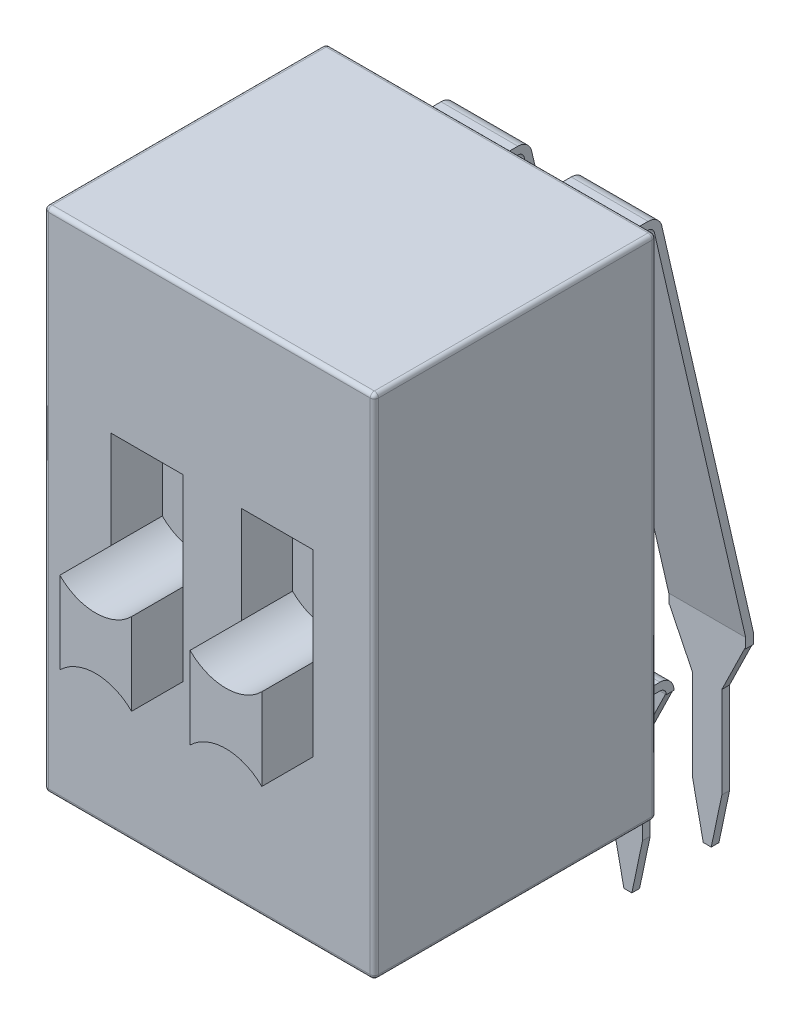
SolidWorks part; units mm, degrees
note: The reader was unsure of these and kept them because the rebuilt part matched: shared geometry of "Эскиз4<4>", "Эскиз5<4>".
ref_plane "Спереди" through (0, 0, 0) normal (0, 0, 1) x (1, 0, 0)
ref_plane "Сверху" through (0, 0, 0) normal (0, 1, 0) x (1, 0, 0)
ref_plane "Справа" through (0, 0, 0) normal (1, 0, 0) x (0, 0, -1)
sketch "Эскиз1" plane through (0, 0, 0) normal (1, 0, 0) x (0, 0, -1)
  line L0 (0, 0) -> (-2.75, 0) construction
  line L1 (-2.75, 4.95) -> (2.75, 4.95)
  line L2 (-2.75, 4.95) -> (-2.75, -4.95)
  line L3 (-2.75, -4.95) -> (2.75, -4.95)
  line L4 (2.75, 4.95) -> (2.75, -4.95)
  line L5 (0, 0) -> (0, -4.95) construction
  dimension "D1" = 5.5
  dimension "D2" = 9.9
extrude "Вытянуть1" add sketch "Эскиз1" along normal blind 6.44
sketch "Эскиз2" plane through (0, 0, -2.75) normal (0, 0, -1) x (-1, 0, 0)
  line L0 (-4.49, 4.95) -> (-4.49, -4.95) construction
  line L1 (-6.44, 4.95) -> (0, 4.95) construction
  line L2 (-6.44, -4.95) -> (0, -4.95) construction
  line L3 (-1.95, 4.95) -> (-1.95, -4.95) construction
  line L4 (-6.44, 3.95) -> (0, 3.95) construction
  line L5 (-6.44, -4.95) -> (-6.44, 4.95) construction
  line L6 (0, -4.95) -> (0, 4.95) construction
  line L7 (-6.44, -3.95) -> (0, -3.95) construction
  line L9 (-5.24, 4.025) -> (-3.74, 4.025)
  line L10 (-5.24, 4.025) -> (-5.24, 3.875)
  line L11 (-5.24, 3.875) -> (-3.74, 3.875)
  line L12 (-3.74, 4.025) -> (-3.74, 3.875)
  line L13 (-5.24, -3.875) -> (-3.74, -3.875) construction
  line L14 (-5.24, -3.875) -> (-5.24, -4.025) construction
  line L15 (-5.24, -4.025) -> (-3.74, -4.025) construction
  line L16 (-3.74, -3.875) -> (-3.74, -4.025) construction
  point P20 (-4.49, 3.875)
  point P21 (-3.74, 3.95)
  point P26 (-3.74, -3.95)
  point P27 (-4.49, -4.025)
  dimension "D1" = 1.95
  dimension "D2" = 1.95
  dimension "D3" = 2.54
  dimension "D4" = 1
  dimension "D5" = 1
  dimension "D6" = 1.5
  dimension "D7" = 0.15
sketch3d "Трехмерный эскиз1"
  line L1 (4.49, 3.95, -2.75) -> (4.49, 3.95, -3.7908)
  line L2 (4.49, 3.7949, -3.9857) -> (4.49, -3.95, -5.7697)
  line L3 (4.49, -3.95, -5.7697) -> (4.49, -7.85, -5.7697)
  line L4 (4.49, 4.95, -2.75) -> (4.49, -4.95, -2.75) construction
  line L5 (6.44, 3.95, -2.75) -> (0, 3.95, -2.75) construction
  line L6 (4.49, -3.95, -2.75) -> (4.49, -3.95, -12.5553) construction
  line L7 (4.49, -7.85, -3.0297) -> (4.49, -7.85, -12.4699) construction
  line L8 (6.44, -3.95, -2.75) -> (0, -3.95, -2.75) construction
  line L10 (6.44, 4.95, 2.75) -> (6.44, -4.95, 2.75) construction
  arc A1 (4.49, 3.95, -3.7908) -> (4.49, 3.7949, -3.9857) centre (4.49, 3.75, -3.7908) ccw
  point P22 (4.49, 3.95, -3.95)
  point P23 (4.29, 3.75, -3.7908)
  dimension "D1" = 8.74
  dimension "D2" = 2.9
sweep "По траектории1" add profiles "Эскиз2" path "Трехмерный эскиз1"
pattern_linear "Линейный массив1" count 2 spacing 2.54 along (-1, 0, 0) of "По траектории1"
sketch3d "Трехмерный эскиз2"
  line L0 (4.49, 4.95, -2.75) -> (4.49, -4.95, -2.75) construction
  line L1 (4.49, -3.95, -2.75) -> (4.49, -3.95, -4.0214)
  line L3 (6.44, -3.95, -2.75) -> (0, -3.95, -2.75) construction
  line L6 (4.49, -4.15, -4.2214) -> (4.49, -7.85, -4.2214)
  arc A0 (4.49, -3.95, -4.0214) -> (4.49, -4.15, -4.2214) centre (4.49, -4.15, -4.0214) ccw
  point P9 (4.49, -3.95, -4.2214)
  point P10 (4.29, -4.15, -4.0214)
  dimension "D1" = 0.2
sketch "Эскиз3" plane through (0, 0, -2.75) normal (0, 0, -1) x (-1, 0, 0)
  line L1 (-5.24, -3.875) -> (-3.74, -3.875)
  line L2 (-5.24, -3.875) -> (-5.24, -4.025)
  line L3 (-5.24, -4.025) -> (-3.74, -4.025)
  line L4 (-3.74, -3.875) -> (-3.74, -4.025)
sweep "По траектории2" add profiles "Эскиз3" path "Трехмерный эскиз2"
pattern_linear "Линейный массив2" count 2 spacing 2.54 along (-1, 0, 0) of "По траектории2"
sketch "Эскиз4" plane through (0, 0, -5.8447) normal (0, 0, -1) x (-1, 0, 0)
  line L0 (-4.49, -3.9415) -> (-4.49, -7.85) construction
  line L1 (-5.24, -3.9415) -> (-3.74, -3.9415) construction
  line L2 (-3.74, -7.85) -> (-5.24, -7.85) construction
  line L3 (-1.95, -3.9415) -> (-1.95, -7.85) construction
  line L4 (-2.7, -3.9415) -> (-1.2, -3.9415) construction
  line L5 (-1.2, -7.85) -> (-2.7, -7.85) construction
  line L6 (-1.8593, -7.85) -> (-2.0407, -7.85)
  line L7 (-2.25, -6.85) -> (-2.25, -5.0707)
  line L8 (-2.25, -5.0707) -> (-2.7, -4.15)
  line L9 (-2.0407, -7.85) -> (-2.25, -6.85)
  line L10 (-2.7, -4.15) -> (-1.2, -4.15) construction
  line L11 (-2.7, -3.9415) -> (-2.7, -7.85) construction
  line L12 (-5.24, -3.9415) -> (-5.24, -7.85) construction
  line L13 (-1.8593, -7.85) -> (-1.65, -6.85)
  line L14 (-1.65, -6.85) -> (-1.65, -5.0707)
  line L15 (-1.65, -5.0707) -> (-1.2, -4.15)
  line L16 (-1.2, -4.15) -> (-2.7, -4.15) construction
  line L17 (-5.24, -4.15) -> (-4.79, -5.0707)
  line L18 (-4.79, -5.0707) -> (-4.79, -6.85)
  line L19 (-4.79, -6.85) -> (-4.58, -7.85)
  line L20 (-4.58, -7.85) -> (-4.4, -7.85)
  line L21 (-4.19, -6.85) -> (-4.4, -7.85)
  line L22 (-4.19, -5.0707) -> (-4.19, -6.85)
  line L23 (-3.74, -4.15) -> (-4.19, -5.0707)
  line L24 (-5.24, -4.15) -> (-3.74, -4.15) construction
  point P17 (-1.95, -4.15)
  point P18 (-4.49, -4.15)
  dimension "D2" = 0.6
  dimension "D3" = 0.3
  dimension "D4" = 0.1814
  dimension "D5" = 0.09
extrude "Вырез-Вытянуть-Тонкостенный1" cut sketch "Эскиз4" along normal blind 0.15 and the other way blind 0.15 flip side to cut thin contours L15 L14 L13 L6 L9 L7 L8 thin type two direction wall 0.015 second wall 0.015
extrude "Вырез-Вытянуть-Тонкостенный4" cut sketch "Эскиз4<4>" against normal blind 0.15 and the other way blind 0.15 thin contours L17 L18 L19 L20 L21 L22 L23 thin type two direction wall 0.015 second wall 0.015
sketch "Эскиз4<4>" plane through (0, 0, -5.8447) normal (0, 0, -1) x (-1, 0, 0) same geometry as "Эскиз4"
sketch "Эскиз5" plane through (0, 0, -4.1464) normal (0, 0, 1) x (1, 0, 0)
  line L0 (1.2, -4.15) -> (1.65, -5.0707)
  line L1 (1.65, -5.0707) -> (1.65, -6.85)
  line L2 (1.65, -6.85) -> (1.8593, -7.85)
  line L3 (1.8593, -7.85) -> (2.0407, -7.85)
  line L4 (2.0407, -7.85) -> (2.25, -6.85)
  line L5 (2.25, -6.85) -> (2.25, -5.0707)
  line L6 (2.25, -5.0707) -> (2.7, -4.15)
  line L7 (2.7, -4.15) -> (1.2, -4.15) construction
  line L8 (3.74, -4.15) -> (5.24, -4.15) construction
  line L9 (5.24, -4.15) -> (4.79, -5.0707)
  line L10 (4.79, -5.0707) -> (4.79, -6.85)
  line L11 (4.79, -6.85) -> (4.58, -7.85)
  line L12 (4.58, -7.85) -> (4.4, -7.85)
  line L13 (4.4, -7.85) -> (4.19, -6.85)
  line L14 (4.19, -6.85) -> (4.19, -5.0707)
  line L15 (4.19, -5.0707) -> (3.74, -4.15)
  line L16 (4.49, -3.9415) -> (4.49, -7.85) construction
  line L17 (4.79, -5.0707) -> (4.19, -5.0707) construction
  line L18 (4.79, -6.85) -> (4.19, -6.85) construction
  line L19 (2.25, -5.0707) -> (1.65, -5.0707) construction
  line L20 (2.25, -6.85) -> (1.65, -6.85) construction
  line L21 (1.95, -3.9415) -> (1.95, -7.85) construction
  point P36 (1.95, -5.0707)
  point P37 (4.49, -5.0707)
  point P38 (4.49, -6.85)
  point P39 (1.95, -6.85)
  point P40 (4.49, -4.15)
  point P41 (1.95, -4.15)
  dimension "D1" = 0.6
  dimension "D2" = 0.6
  dimension "D3" = 0.18
  dimension "D4" = 0.1814
extrude "Вырез-Вытянуть-Тонкостенный5" cut sketch "Эскиз5" against normal blind 0.15 and the other way blind 0.15 thin contours L0 L1 L2 L3 L4 L5 L6
extrude "Вырез-Вытянуть-Тонкостенный6" cut sketch "Эскиз5<4>" against normal blind 0.15 and the other way blind 0.15 thin contours L9 L10 L11 L12 L13 L14 L15 thin type two direction wall 0.015 second wall 0.015
sketch "Эскиз5<4>" plane through (0, 0, -4.1464) normal (0, 0, 1) x (1, 0, 0) same geometry as "Эскиз5"
sketch "Эскиз6" plane through (0, 0, 2.75) normal (0, 0, 1) x (1, 0, 0)
  line L0 (1.95, -7.835) -> (1.95, 4.95) construction
  line L1 (2.0285, -7.835) -> (1.8715, -7.835) construction
  line L2 (6.44, 4.95) -> (0, 4.95) construction
  line L3 (4.49, -7.835) -> (4.49, 4.95) construction
  line L4 (4.4122, -7.835) -> (4.5678, -7.835) construction
  line L5 (0, 0) -> (6.44, 0) construction
  line L6 (1.3046, 1.75) -> (2.7046, 1.75)
  line L7 (1.3046, 1.75) -> (1.3046, -1.75)
  line L8 (1.3046, -1.75) -> (2.7046, -1.75)
  line L9 (2.7046, 1.75) -> (2.7046, -1.75)
  line L10 (6.44, 4.95) -> (6.44, -4.95) construction
  point P14 (1.3046, 0)
  dimension "D1" = 1.4
  dimension "D2" = 3.5
extrude "Вырез-Вытянуть1" cut sketch "Эскиз6" against normal blind 1
pattern_linear "Линейный массив3" count 2 spacing 2.54 along (1, 0, 0) of "Вырез-Вытянуть1"
sketch "Эскиз7" plane through (0, 0, 1.75) normal (0, 0, 1) x (1, 0, 0)
  line L2 (1.3046, -0.15) -> (1.3046, -1.75)
  line L4 (2.7046, -0.15) -> (2.7046, -1.75)
  line L9 (3.8446, -0.15) -> (3.8446, -1.75)
  line L11 (5.2446, -0.15) -> (5.2446, -1.75)
  arc A0 (1.3046, -1.75) -> (2.7046, -1.75) centre (2.0046, -2.45) cw
  arc A1 (1.3046, -0.15) -> (2.7046, -0.15) centre (2.0046, 0.55) ccw
  arc A2 (3.8446, -0.15) -> (5.2446, -0.15) centre (4.5446, 0.55) ccw
  arc A3 (3.8446, -1.75) -> (5.2446, -1.75) centre (4.5446, -2.45) cw
  dimension "D1" = 1.6
extrude "Вытянуть2" add sketch "Эскиз7" along normal blind 2
sketch "Эскиз8" plane through (0, 0, -2.75) normal (0, 0, -1) x (-1, 0, 0)
  line L0 (0, 0) -> (-6.4476, 0) construction
  line L1 (-5.9679, 2.4) -> (-0.4721, 2.4)
  line L2 (-5.9679, 2.4) -> (-5.9679, 2)
  line L3 (-5.9679, 2) -> (-0.4721, 2)
  line L4 (-0.4721, 2.4) -> (-0.4721, 2)
  line L5 (-3.22, 4.95) -> (-3.22, -4.95) construction
  line L6 (-5.9679, -2) -> (-0.4721, -2)
  line L7 (-5.9679, -2) -> (-5.9679, -2.4)
  line L8 (-5.9679, -2.4) -> (-0.4721, -2.4)
  line L9 (-0.4721, -2) -> (-0.4721, -2.4)
  line L10 (-6.44, 4.95) -> (0, 4.95) construction
  line L11 (-6.44, -4.95) -> (0, -4.95) construction
  point P17 (-3.22, 2.4)
  point P18 (-3.22, -2)
  dimension "D1" = 2
  dimension "D2" = 0.4
  dimension "D3" = 2
  dimension "D4" = 5.4959
extrude "Вытянуть3" add sketch "Эскиз8" along normal blind 0.4
fillet "Скругление1" radius 0.08 12 edges at (3.22, 4.95, -2.75) (3.22, 4.95, 2.75) (6.44, 4.95, 0) (6.44, 0, -2.75) (6.44, 0, 2.75) (3.22, -4.95, 2.75) (6.44, -4.95, 0) (3.22, -4.95, -2.75) (0, -4.95, 0) (0, 0, -2.75) (0, 4.95, 0) (0, 0, 2.75)
